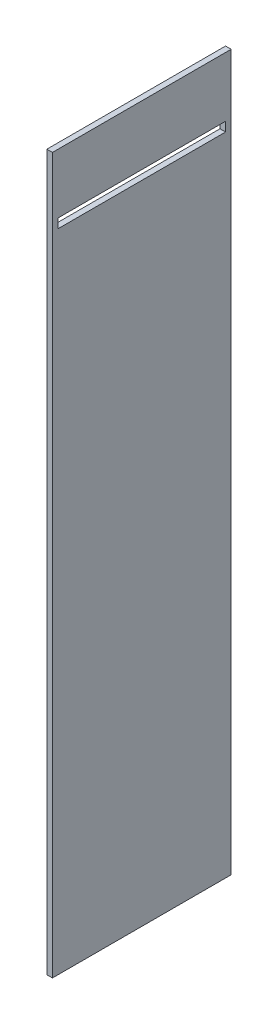
SolidWorks part; units mm, degrees
ref_plane "Front Plane" through (0, 0, 0) normal (0, 0, 1) x (1, 0, 0)
ref_plane "Top Plane" through (0, 0, 0) normal (0, 1, 0) x (1, 0, 0)
ref_plane "Right Plane" through (0, 0, 0) normal (1, 0, 0) x (0, 0, -1)
sketch "Sketch1" plane through (0, 0, 0) normal (0, 1, 0) x (1, 0, 0)
  line L1 (0, 0) -> (4.7625, 0)
  line L2 (0, 0) -> (0, 152.4)
  line L3 (0, 152.4) -> (4.7625, 152.4)
  line L4 (4.7625, 0) -> (4.7625, 152.4)
  dimension "D1" = 152.4
  dimension "D2" = 4.7625
extrude "Boss-Extrude1" add sketch "Sketch1" along normal blind 609.6
sketch "Sketch2" plane through (4.7625, 0, 0) normal (1, 0, 0) x (0, 0, -1)
  line L1 (147.6375, 558.8) -> (4.7625, 558.8)
  line L2 (147.6375, 558.8) -> (147.6375, 550.8625)
  line L3 (147.6375, 550.8625) -> (4.7625, 550.8625)
  line L4 (4.7625, 558.8) -> (4.7625, 550.8625)
extrude "Cut-Extrude1" cut sketch "Sketch2" against normal through all
